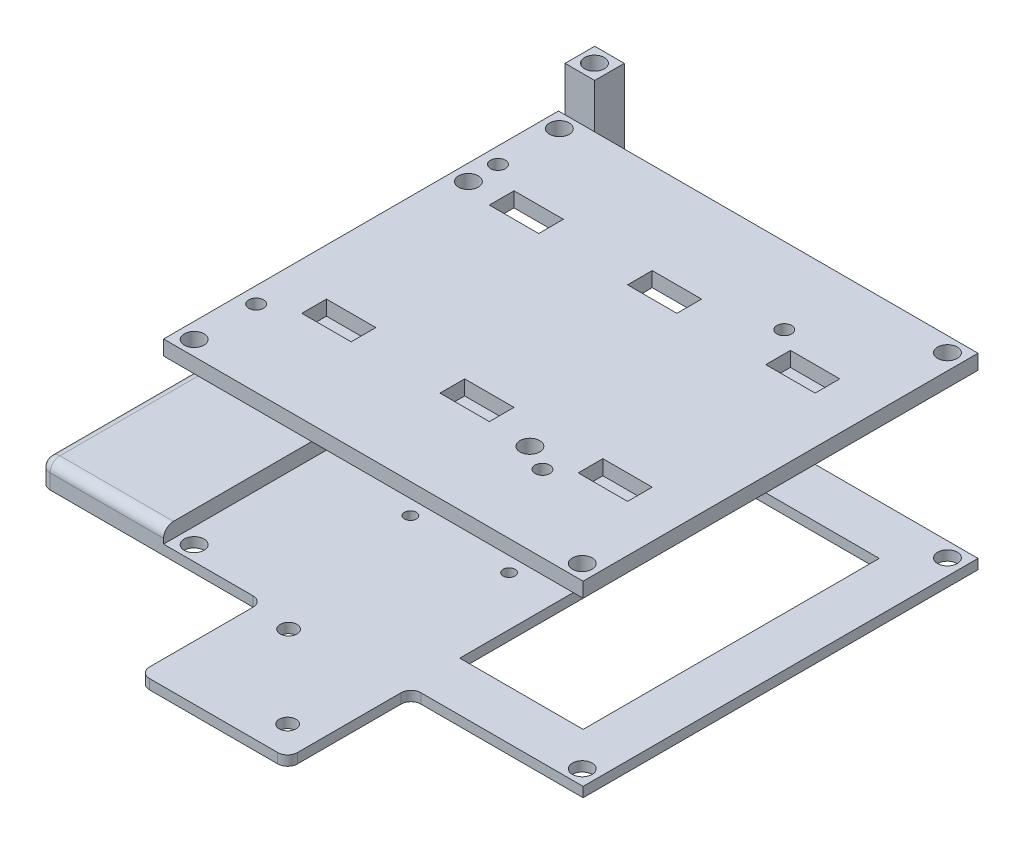
SolidWorks part; units mm, degrees
ref_plane "Front Plane" through (0, 0, 0) normal (0, 0, 1) x (1, 0, 0)
ref_plane "Top Plane" through (0, 0, 0) normal (0, 1, 0) x (1, 0, 0)
ref_plane "Right Plane" through (0, 0, 0) normal (1, 0, 0) x (0, 0, -1)
sketch "Sketch1" plane through (0, 0, 0) normal (0, 1, 0) x (1, 0, 0)
  line L1 (-48.1422, 42.8607) -> (61.8578, 42.8607)
  line L2 (-48.1422, 42.8607) -> (-48.1422, -37.1393)
  line L3 (-48.1422, -37.1393) -> (61.8578, -37.1393)
  line L4 (61.8578, 42.8607) -> (61.8578, -37.1393)
  line L5 (-3.1422, 42.8607) -> (26.8578, 42.8607)
  line L6 (-3.1422, 42.8607) -> (-3.1422, 69.8607)
  line L7 (-3.1422, 69.8607) -> (26.8578, 69.8607)
  line L8 (26.8578, 42.8607) -> (26.8578, 69.8607)
  line L9 (-3.0177, -37.1393) -> (26.9823, -37.1393)
  line L10 (-3.0177, -37.1393) -> (-3.0177, -62.1393)
  line L11 (-3.0177, -62.1393) -> (26.9823, -62.1393)
  line L12 (26.9823, -37.1393) -> (26.9823, -62.1393)
  dimension "D1" = 110
  dimension "D2" = 80
  dimension "D3" = 27
  dimension "D5" = 30
  dimension "D6" = 25
extrude "Boss-Extrude1" add sketch "Sketch1" along normal blind 2 contours L10 L9 L12 L11 | L2 L1 L4 L3 | L6 L5 L8 L7
sketch "Sketch2" plane through (0, 2, 0) normal (0, 1, 0) x (1, 0, 0)
  line L0 (-48.1422, -37.1393) -> (-3.0177, -37.1393) construction
  line L1 (-48.1422, 42.8607) -> (-23.1422, 42.8607)
  line L2 (-48.1422, 42.8607) -> (-48.1422, -37.1393)
  line L3 (-48.1422, -37.1393) -> (-23.1422, -37.1393)
  line L4 (-23.1422, 42.8607) -> (-23.1422, -37.1393)
  dimension "D1" = 25
extrude "Boss-Extrude2" add sketch "Sketch2" along normal blind 3
sketch "Sketch3" plane through (0, 5, 0) normal (0, 1, 0) x (1, 0, 0)
  line L0 (-48.1422, 42.8607) -> (-48.1422, -37.1393) construction
  line L1 (-23.1422, 42.8607) -> (-48.1422, 42.8607) construction
  circle A0 centre (-35.6422, 2.8607) radius 3.375
  dimension "D1" = 12.5
  dimension "D2" = 40
extrude "Cut-Extrude1" cut sketch "Sketch3" against normal blind 6
sketch "Sketch4" plane through (0, 2, 0) normal (0, 1, 0) x (1, 0, 0)
  line L0 (-23.1422, 42.8607) -> (-3.1422, 42.8607) construction
  line L1 (-48.1422, 42.8607) -> (-48.1422, -37.1393) construction
  line L2 (-3.1422, 12.8607) -> (16.8578, 12.8607) construction
  line L3 (-3.1422, 12.8607) -> (-3.1422, -7.1393) construction
  circle A0 centre (-3.1422, 12.8607) radius 1.2
  circle A1 centre (16.8578, 12.8607) radius 1.2
  circle A2 centre (16.8578, -7.1393) radius 1.2
  circle A3 centre (-3.1422, -7.1393) radius 1.2
  dimension "D1" = 30
  dimension "D2" = 45
  dimension "D4" = 20
  dimension "D5" = 20
  dimension "D3" = 2
extrude "Cut-Extrude2" cut sketch "Sketch4" against normal blind 6
sketch "Sketch5" plane through (0, 2, 0) normal (0, 1, 0) x (1, 0, 0)
  line L0 (-3.1422, 42.8607) -> (-3.1422, 69.8607) construction
  line L1 (-3.1422, 69.8607) -> (26.8578, 69.8607) construction
  line L2 (1.8578, 64.8607) -> (21.8578, 64.8607) construction
  line L3 (1.8578, 64.8607) -> (1.8578, 44.8607) construction
  line L4 (20.9823, -56.1393) -> (4.4323, -56.1393) construction
  line L5 (4.4323, -56.1393) -> (4.4323, -39.3893) construction
  line L6 (26.9823, -37.1393) -> (26.9823, -62.1393) construction
  line L7 (-3.0177, -62.1393) -> (26.9823, -62.1393) construction
  circle A0 centre (1.8578, 64.8607) radius 1.7
  circle A1 centre (21.8578, 64.8607) radius 1.7
  circle A2 centre (21.8578, 44.8607) radius 1.7
  circle A3 centre (1.8578, 44.8607) radius 1.7
  circle A4 centre (20.9823, -56.1393) radius 1.7
  circle A5 centre (4.4323, -39.3893) radius 1.7
  dimension "D1" = 5
  dimension "D5" = 16.55
  dimension "D7" = 6
  dimension "D9" = 3.4
  dimension "D2" = 5
  dimension "D3" = 20
  dimension "D4" = 20
  dimension "D6" = 16.75
  dimension "D8" = 6
extrude "Cut-Extrude3" cut sketch "Sketch5" against normal blind 6
sketch "Sketch6" plane through (0, 2, 0) normal (0, 1, 0) x (1, 0, 0)
  line L0 (-48.1422, 2.8607) -> (59.7758, 2.8607) construction
  line L1 (-23.1422, 42.8607) -> (-18.1422, 42.8607)
  line L2 (-23.1422, 42.8607) -> (-23.1422, 37.8607)
  line L3 (-23.1422, 37.8607) -> (-18.1422, 37.8607)
  line L4 (-18.1422, 42.8607) -> (-18.1422, 37.8607)
  line L5 (-48.1422, 42.8607) -> (-48.1422, -37.1393) construction
  line L6 (61.8578, -32.1393) -> (56.8578, -32.1393)
  line L7 (61.8578, 42.8607) -> (56.8578, 42.8607)
  line L8 (61.8578, 42.8607) -> (61.8578, 37.8607)
  line L9 (61.8578, 37.8607) -> (56.8578, 37.8607)
  line L10 (56.8578, 42.8607) -> (56.8578, 37.8607)
  line L11 (56.8578, -37.1393) -> (56.8578, -32.1393)
  line L12 (61.8578, -37.1393) -> (56.8578, -37.1393)
  line L13 (61.8578, -37.1393) -> (61.8578, -32.1393)
  point P22 (-18.1422, -32.1393)
  point P23 (-18.1422, -32.1393)
  point P24 (-18.1422, -32.1393)
  dimension "D1" = 5
  dimension "D2" = 5
  dimension "D3" = 5
  dimension "D4" = 5
sketch "Sketch7" plane through (0, 35, 0) normal (0, 1, 0) x (1, 0, 0)
  line L1 (-23.1422, 42.8607) -> (61.8578, 42.8607)
  line L2 (-23.1422, 42.8607) -> (-23.1422, -37.1393)
  line L3 (-23.1422, -37.1393) -> (61.8578, -37.1393)
  line L4 (61.8578, 42.8607) -> (61.8578, -37.1393)
extrude "Boss-Extrude4" add sketch "Sketch7" along normal blind 3
sketch "Sketch8" plane through (0, 38, 0) normal (0, 1, 0) x (1, 0, 0)
  line L0 (-23.1422, 42.8607) -> (-23.1422, -37.1393) construction
  line L1 (61.8578, 42.8607) -> (-23.1422, 42.8607) construction
  line L2 (-19.8922, 27.3607) -> (-19.8922, -21.6393) construction
  line L3 (-23.1422, -37.1393) -> (-23.1422, 42.8607) construction
  circle A0 centre (-19.8922, 27.3607) radius 1.5
  circle A1 centre (38.1078, 27.3607) radius 1.5
  circle A2 centre (38.1078, -21.6393) radius 1.5
  circle A3 centre (-19.8922, -21.6393) radius 1.5
  circle A4 centre (-19.8922, 21.3607) radius 2
  circle A5 centre (32.7875, -18.8655) radius 2
  dimension "D1" = 3.25
  dimension "D4" = 3.25
  dimension "D6" = 6
  dimension "D2" = 15.5
  dimension "D3" = 49
  dimension "D5" = 6
  dimension "D7" = 2
  dimension "D8" = 2
sketch "Sketch9" plane through (0, 38, 0) normal (0, 1, 0) x (1, 0, 0)
  line L0 (61.8578, 42.8607) -> (-23.1422, 42.8607) construction
  line L1 (14.3578, 24.3607) -> (24.3578, 24.3607)
  line L2 (14.3578, 24.3607) -> (14.3578, 19.3607)
  line L3 (14.3578, 19.3607) -> (24.3578, 19.3607)
  line L4 (24.3578, 24.3607) -> (24.3578, 19.3607)
  line L5 (-23.1422, 2.8607) -> (57.9157, 2.8607) construction
  line L6 (-13.6422, 24.3607) -> (-3.6422, 24.3607)
  line L7 (-13.6422, 24.3607) -> (-13.6422, 19.3607)
  line L8 (-13.6422, 19.3607) -> (-3.6422, 19.3607)
  line L9 (-3.6422, 24.3607) -> (-3.6422, 19.3607)
  line L10 (-23.1422, 42.8607) -> (-23.1422, -37.1393) construction
  line L11 (42.3578, -13.6393) -> (52.3578, -13.6393)
  line L12 (42.3578, 24.3607) -> (52.3578, 24.3607)
  line L13 (42.3578, 24.3607) -> (42.3578, 19.3607)
  line L14 (42.3578, 19.3607) -> (52.3578, 19.3607)
  line L15 (52.3578, 24.3607) -> (52.3578, 19.3607)
  line L16 (52.3578, -18.6393) -> (52.3578, -13.6393)
  line L17 (42.3578, -18.6393) -> (52.3578, -18.6393)
  line L18 (42.3578, -18.6393) -> (42.3578, -13.6393)
  line L19 (14.3578, -13.6393) -> (24.3578, -13.6393)
  line L20 (24.3578, -18.6393) -> (24.3578, -13.6393)
  line L21 (14.3578, -18.6393) -> (24.3578, -18.6393)
  line L22 (14.3578, -18.6393) -> (14.3578, -13.6393)
  line L23 (-13.6422, -13.6393) -> (-3.6422, -13.6393)
  line L24 (-3.6422, -18.6393) -> (-3.6422, -13.6393)
  line L25 (-13.6422, -18.6393) -> (-3.6422, -18.6393)
  line L26 (-13.6422, -18.6393) -> (-13.6422, -13.6393)
  dimension "D1" = 5
  dimension "D2" = 18.5
  dimension "D3" = 10
  dimension "D4" = 10
  dimension "D5" = 5
  dimension "D6" = 18
  dimension "D7" = 37.5
  dimension "D8" = 10
  dimension "D9" = 18
  dimension "D10" = 18.5
  dimension "D11" = 18.5
  dimension "D12" = 5
sketch "Sketch10" plane through (0, 2, 0) normal (0, 1, 0) x (1, 0, 0)
  line L0 (26.9823, -37.1393) -> (61.8578, -37.1393) construction
  line L1 (26.8578, 32.8607) -> (51.8578, 32.8607)
  line L2 (26.8578, 32.8607) -> (26.8578, -27.1393)
  line L3 (26.8578, -27.1393) -> (51.8578, -27.1393)
  line L4 (51.8578, 32.8607) -> (51.8578, -27.1393)
  line L5 (61.8578, 42.8607) -> (61.8578, -37.1393) construction
  dimension "D1" = 60
  dimension "D2" = 10
  dimension "D3" = 10
  dimension "D4" = 25
extrude "Cut-Extrude6" cut sketch "Sketch10" against normal blind 4
extrude "Cut-Extrude7" cut sketch "Sketch8" against normal blind 10 and the other way blind 10
extrude "Cut-Extrude8" cut sketch "Sketch9" against normal blind 10 and the other way blind 10
sketch "Sketch11" plane through (0, 38, 0) normal (0, 1, 0) x (1, 0, 0)
  circle A0 centre (-19.9578, 39.8532) radius 2
  circle A1 centre (-19.9578, -34.1317) radius 2
  circle A2 centre (58.6735, -34.1317) radius 2
  circle A3 centre (58.6735, 39.8532) radius 2
  point P12 (-19.3862, 39.3917)
  point P13 (-19.9578, 39.8532)
extrude "Cut-Extrude9" cut sketch "Sketch11" against normal through all
fillet "Fillet1" radius 2 13 edges at (26.8578, 1, -69.8607) (26.8578, 1, -42.8607) (-3.1422, 1, -69.8607) (-3.1422, 1, -42.8607) (-3.0177, 1, 62.1393) (26.9823, 1, 62.1393) (26.9823, 1, 37.1393) (-3.0177, 1, 37.1393) (-48.1422, 5, -2.8607) (-35.6422, 5, -42.8607) (-35.6422, 5, 37.1393) (-48.1422, 2.5, 37.1393) (-48.1422, 2.5, -42.8607)
sketch "Sketch14" plane through (0, 0, 0) normal (0, 1, 0) x (1, 0, 0)
  line L1 (-38.8328, 65.8947) -> (-32.8328, 65.8947)
  line L2 (-38.8328, 65.8947) -> (-38.8328, 59.8947)
  line L3 (-38.8328, 59.8947) -> (-32.8328, 59.8947)
  line L4 (-32.8328, 65.8947) -> (-32.8328, 59.8947)
  circle A0 centre (-35.8834, 62.8947) radius 2
  point P6 (-37.8757, 64.8947)
  point P7 (0, 0)
  point P8 (-37.8328, 64.815)
  point P9 (-35.7205, 62.8411)
  point P10 (-35.8328, 62.8178)
  point P11 (-35.8834, 62.8947)
  dimension "D1" = 6
  dimension "D2" = 6
extrude "Boss-Extrude5" add sketch "Sketch14" along normal blind 30 separate body
sketch "Sketch15" plane through (0, 38, 0) normal (0, 1, 0) x (1, 0, 0)
  line L1 (-22.8948, 42.5659) -> (-16.7549, 42.5659)
  line L2 (-22.8948, 42.5659) -> (-22.8948, 36.5942)
  line L3 (-22.8948, 36.5942) -> (-16.7549, 36.5942)
  line L4 (-16.7549, 42.5659) -> (-16.7549, 36.5942)
  dimension "D1" = 6.1399
  dimension "D2" = 5.9717
